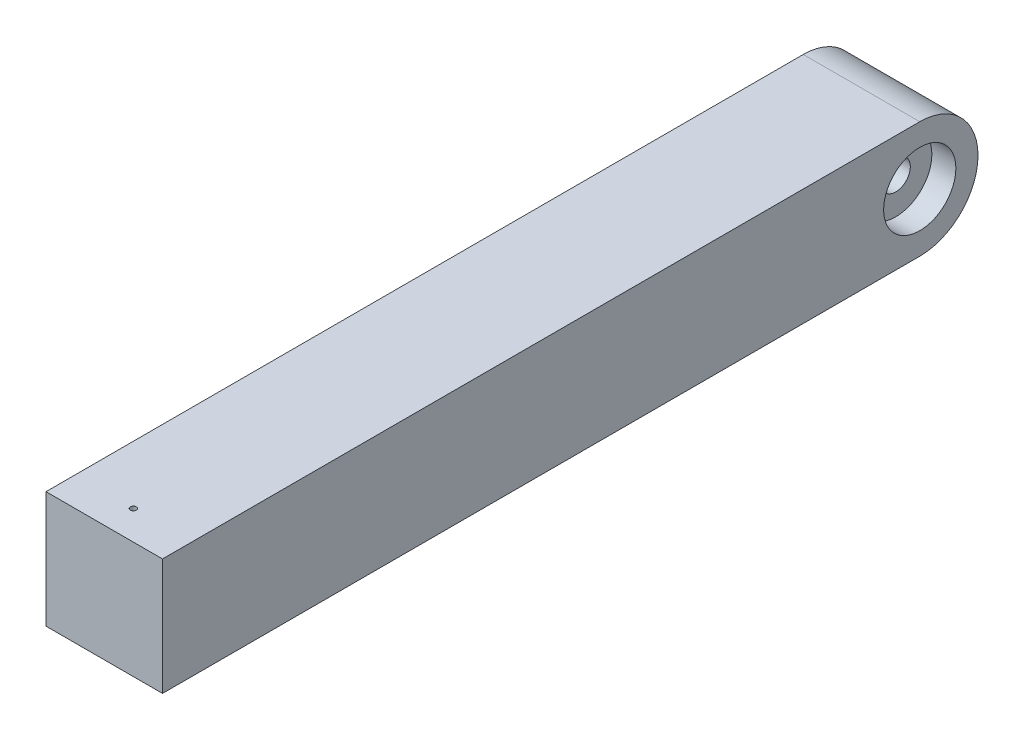
SolidWorks part; units mm, degrees
ref_plane "Front Plane" through (0, 0, 0) normal (1, 0, 0) x (0, 1, 0)
ref_plane "Top Plane" through (0, 0, 0) normal (0, 0, 1) x (0, 1, 0)
ref_plane "Right Plane" through (0, 0, 0) normal (0, 1, 0) x (-1, 0, 0)
sketch "Sketch1" plane through (0, 0, 0) normal (0, 0, 1) x (0, 1, 0)
  line L1 (-50, 50) -> (50, 50)
  line L2 (-50, 50) -> (-50, -50)
  line L3 (-50, -50) -> (50, -50)
  line L4 (50, 50) -> (50, -50)
  point P4 (-50, 0)
  point P6 (0, 50)
  dimension "D1" = 100
  dimension "D2" = 100
  dimension "D3" = 0
  dimension "D4" = 0
extrude "Boss-Extrude1" add sketch "Sketch1" against normal blind 700
fillet "Fillet1" radius 50 2 edges at (0, -50, -700) (0, 50, -700)
sketch "Sketch2" plane through (50, 0, 0) normal (1, 0, 0) x (0, 1, 0)
  line L3 (-50, 0) -> (-50, -650)
  line L4 (50, -650) -> (50, 0)
  line L5 (50, 0) -> (-50, 0)
  line L6 (-50, 0) -> (-50, -650)
  line L7 (50, -650) -> (50, 0)
  line L8 (50, 0) -> (-50, 0)
  circle A0 centre (0, -650) radius 31
  arc A2 (-50, -650) -> (0, -700) centre (0, -650) ccw
  arc A3 (0, -700) -> (50, -650) centre (0, -650) ccw
  arc A4 (-50, -650) -> (0, -700) centre (0, -650) ccw
  arc A5 (0, -700) -> (50, -650) centre (0, -650) ccw
  dimension "D2" = 62
  dimension "D1" = 0
extrude "Cut-Extrude1" cut sketch "Sketch2" against normal up to surface (100 mm away) contours A0 region at (50, 0, -650) up to face at (-50, 0, -404.1421)
hole_wizard "Ø5.0mm Dowel Hole1" positions "Sketch4" profile "Sketch5" hole size "Ø5.0" standard "IS" end condition through all
sketch "Sketch4" plane through (0, -50, 0) normal (0, -1, 0) x (1, 0, 0)
  point P0 (0, -25)
  dimension "D1" = 25
sketch "Sketch5" plane through (0, -50, -25) normal (1, 0, 0) x (0, 0, -1)
  line L0 (0, 0) -> (0, 100)
  line L1 (0, 100) -> (2.5, 100)
  line L2 (2.5, 100) -> (2.5, 0.025)
  line L3 (2.5, 0.025) -> (2.525, 0)
  line L5 (2.525, 0) -> (0, 0)
  line L6 (-2.5, 0.025) -> (-2.525, 0) construction
  line L11 (0, -6.35) -> (0, 107.95) construction
  dimension "Thru Hole Dia." = 5
  dimension "Thru Hole Depth" = 100
  dimension "Near C'Sink Dia." = 5.05
  dimension "Near C'Sink Angle" = 90
mirror "Mirror1" about plane through (0, 0, 0) normal (0, 1, 0) of "Ø5.0mm Dowel Hole1"
sketch "Sketch6" plane through (0, 0, 0) normal (1, 0, 0) x (0, 1, 0)
  line L3 (-50, 0) -> (-50, -650)
  line L4 (50, -650) -> (50, 0)
  line L5 (50, 0) -> (-50, 0)
  line L6 (-50, 0) -> (-50, -650)
  line L7 (50, -650) -> (50, 0)
  line L8 (50, 0) -> (-50, 0)
  circle A0 centre (0, -650) radius 31
  circle A1 centre (0, -650) radius 12.5
  arc A2 (-50, -650) -> (0, -700) centre (0, -650) ccw
  arc A3 (0, -700) -> (50, -650) centre (0, -650) ccw
  arc A4 (-50, -650) -> (0, -700) centre (0, -650) ccw
  arc A5 (0, -700) -> (50, -650) centre (0, -650) ccw
  dimension "D2" = 62
  dimension "D3" = 25
  dimension "D1" = 0
extrude "Boss-Extrude2" add sketch "Sketch6" along normal blind 29.4 and the other way blind 29.4 contours A0 A1 region at (0, -30.1232, -650)
